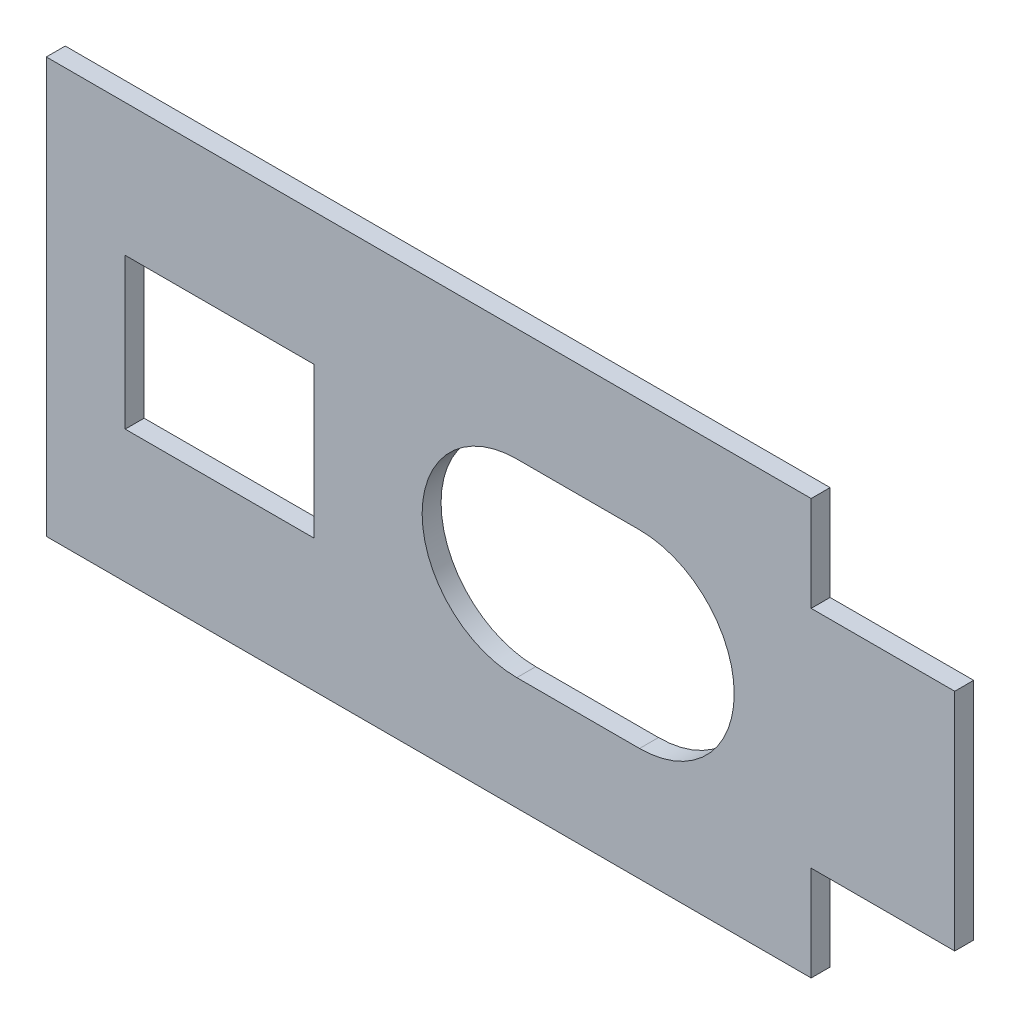
SolidWorks part; units mm, degrees
ref_plane "Front Plane" through (0, 0, 0) normal (0, 0, 1) x (1, 0, 0)
ref_plane "Top Plane" through (0, 0, 0) normal (0, 1, 0) x (1, 0, 0)
ref_plane "Right Plane" through (0, 0, 0) normal (1, 0, 0) x (0, 0, -1)
sketch "Sketch1" plane through (0, 0, 0.762) normal (0, 0, 1) x (1, 0, 0)
  line L0 (-5.2453, -30.2624) -> (-5.2453, -24.7125) construction
  line L1 (1.8413, -24.7125) -> (1.8413, -30.2624) construction
  line L2 (-5.2453, -24.5347) -> (-5.2453, -24.7125) construction
  line L3 (-5.2453, -30.2624) -> (-5.2453, -30.4402) construction
  line L4 (15.7097, -20.7184) -> (-14.1734, -20.7184) construction
  line L12 (-5.2453, -30.2624) -> (-5.2453, -24.7125) construction
  line L13 (-5.2453, -30.4402) -> (6.7816, -30.4402) construction
  line L14 (6.7816, -30.4402) -> (6.7816, -24.5347) construction
  line L15 (6.7816, -24.5347) -> (-5.2453, -24.5347) construction
  line L16 (-5.2453, -30.2624) -> (-5.2453, -24.7125) construction
  line L17 (1.8413, -24.7125) -> (1.8413, -30.2624) construction
  line L18 (-5.2453, -24.5347) -> (-5.2453, -24.7125) construction
  line L19 (-5.2453, -30.2624) -> (-5.2453, -30.4402) construction
  line L20 (-5.2453, -30.2624) -> (-5.2453, -24.7125) construction
  line L21 (-5.2453, -30.4402) -> (6.7816, -30.4402) construction
  line L22 (6.7816, -30.4402) -> (6.7816, -24.5347) construction
  line L23 (6.7816, -24.5347) -> (-5.2453, -24.5347) construction
  line L27 (-5.2453, -30.2624) -> (1.8413, -30.2624) construction
  line L28 (1.8413, -24.7125) -> (-5.2453, -24.7125) construction
  line L31 (-8.6743, -19.1309) -> (22.1091, -19.1309)
  line L32 (-8.6743, -19.1309) -> (-8.6743, -35.8441)
  line L33 (-8.6743, -35.8441) -> (22.1091, -35.8441)
  line L39 (22.1091, -19.1309) -> (22.1091, -22.9599)
  line L45 (27.8876, -22.9599) -> (27.8876, -32.015)
  line L46 (27.8876, -32.015) -> (22.1091, -32.015)
  line L47 (22.1091, -32.015) -> (22.1091, -35.8441)
  line L49 (15.2017, -27.4875) -> (10.2614, -27.4875) construction
  line L54 (15.2017, -31.2975) -> (10.2614, -31.2975)
  line L55 (15.2017, -23.6775) -> (10.2614, -23.6775)
  line L56 (1.8413, -30.2624) -> (6.7816, -30.2624) construction
  line L57 (1.8413, -24.7125) -> (-5.2453, -24.7125) construction
  line L58 (27.8876, -22.9599) -> (26.6176, -22.9599)
  line L59 (26.6176, -22.9599) -> (22.1091, -22.9599)
  line L60 (-5.2453, -30.2624) -> (1.8413, -30.2624) construction
  line L61 (-5.4993, -24.4585) -> (2.0953, -24.4585)
  line L62 (-5.4993, -24.4585) -> (-5.4993, -30.5164)
  line L63 (-5.4993, -30.5164) -> (2.0953, -30.5164)
  line L64 (2.0953, -24.4585) -> (2.0953, -30.5164)
  line L84 (28.5226, -22.9599) -> (28.5226, -32.015) construction
  line L85 (28.5226, -32.015) -> (33.0311, -32.015) construction
  line L86 (33.0311, -32.015) -> (33.0311, -22.9599) construction
  line L87 (33.0311, -22.9599) -> (28.5226, -22.9599) construction
  line L88 (28.5226, -22.9599) -> (28.5226, -32.015) construction
  line L89 (28.5226, -32.015) -> (33.0311, -32.015) construction
  line L90 (33.0311, -32.015) -> (33.0311, -22.9599)
  line L91 (33.0311, -22.9599) -> (28.5226, -22.9599) construction
  circle A0 centre (15.2017, -27.4875) radius 1.319 construction
  circle A1 centre (15.2017, -27.4875) radius 1.319 construction
  arc A2 (15.2017, -31.2975) -> (15.2017, -23.6775) centre (15.2017, -27.4875) ccw
  arc A3 (10.2614, -23.6775) -> (10.2614, -31.2975) centre (10.2614, -27.4875) ccw
  point P1 (27.8876, -27.4875)
  point P3 (-8.6743, -27.4875)
  point P28 (12.7316, -27.4875)
  point P38 (26.6176, -22.9599)
  point P45 (-1.702, -24.4585)
  point P46 (-1.702, -24.7125)
  point P47 (2.0953, -27.4875)
  point P48 (1.8413, -27.4875)
  line M91 (6.7816, -30.4402) -> (-5.2453, -30.4402)
  line M95 (-5.2453, -24.5347) -> (6.7816, -24.5347)
  line M96 (6.7816, -24.5347) -> (6.7816, -30.4402)
  line M97 (15.7097, -20.7184) -> (-14.1734, -20.7184)
  line M101 (-14.1734, -34.2566) -> (15.7097, -34.2566)
  arc M102 (15.7097, -34.2566) -> (18.2497, -31.7166) centre (15.7097, -31.7166) ccw
  line M103 (18.2497, -31.7166) -> (18.2497, -23.2584)
  arc M104 (18.2497, -23.2584) -> (15.7097, -20.7184) centre (15.7097, -23.2584) ccw
  dimension "D4" = 0.635
  dimension "D3" = 3.81
  dimension "D2" = 1.5875
  dimension "D5" = 1.27
  dimension "D7" = 0.254
  dimension "D8" = 0.254
  dimension "D1" = 3.175
extrude "Boss-Extrude2" add sketch "Sketch1" along normal blind 0.762 contours A2 L32 L33 L47 L46 L45 L58 L59 L39 L31 M103 M102 M101 M97 M104 | A3 L55 A2 L32 L54 L64 L63 L62 L61 M103 M104 M97 M101 M102 M96 M91 M95 | A3 L64 M96 M95 M91 region at (6.7174, -19.5329, 0.762) region at (3.5177, -21.0198, 0.762) region at (4.382, -27.4875, 0.762)
